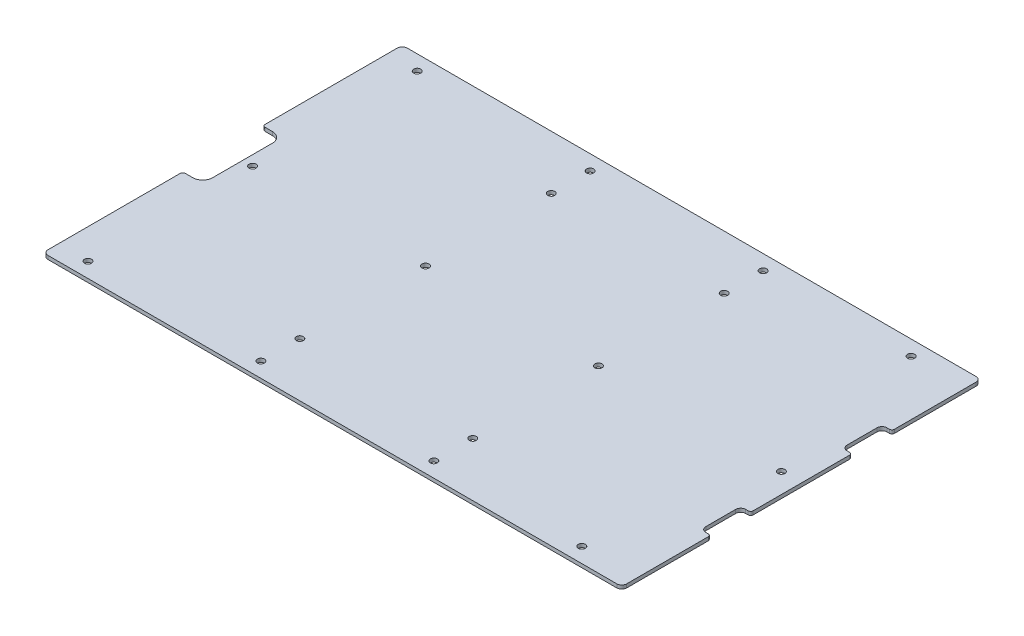
SolidWorks part; units mm, degrees
material "1060 Alloy"
ref_plane "Front" through (0, 0, 0) normal (0, 0, 1) x (1, 0, 0)
ref_plane "Top" through (0, 0, 0) normal (0, 1, 0) x (1, 0, 0)
ref_plane "Right" through (0, 0, 0) normal (1, 0, 0) x (0, 0, -1)
sketch "Sketch1" plane through (0, 0, 0) normal (0, 1, 0) x (1, 0, 0)
  line L0 (-55.0333, 0) -> (-165.1, 0) construction
  line L1 (-180.975, 114.3) -> (180.975, 114.3)
  line L2 (-184.15, 111.125) -> (-184.15, -111.125)
  line L3 (-180.975, -114.3) -> (180.975, -114.3)
  line L4 (184.15, 111.125) -> (184.15, -111.125)
  line L5 (-184.15, 114.3) -> (184.15, -114.3) construction
  line L6 (-184.15, -114.3) -> (184.15, 114.3) construction
  line L7 (-165.1, -104.775) -> (165.1, -104.775) construction
  line L8 (-165.1, -104.775) -> (-165.1, 104.775) construction
  line L9 (-165.1, 104.775) -> (165.1, 104.775) construction
  line L10 (165.1, -104.775) -> (165.1, 104.775) construction
  line L11 (-165.1, -104.775) -> (165.1, 104.775) construction
  line L12 (-165.1, 104.775) -> (165.1, -104.775) construction
  line L13 (-55.0333, -104.775) -> (55.0333, -104.775) construction
  line L14 (-55.0333, -104.775) -> (-55.0333, 104.775) construction
  line L15 (-55.0333, 104.775) -> (55.0333, 104.775) construction
  line L16 (55.0333, -104.775) -> (55.0333, 104.775) construction
  line L17 (-55.0333, -104.775) -> (55.0333, 104.775) construction
  line L18 (-55.0333, 104.775) -> (55.0333, -104.775) construction
  line L19 (55.0333, 0) -> (165.1, 0) construction
  line L20 (-55.0333, 0) -> (55.0333, 0) construction
  line L31 (-55.0291, 80.01) -> (55.0291, 80.01) construction
  line L32 (149.225, -104.775) -> (149.225, 104.775) construction
  line L33 (-55.0291, 80.01) -> (-55.0291, -80.01) construction
  line L34 (-55.0291, -80.01) -> (55.0291, -80.01) construction
  line L35 (55.0291, 80.01) -> (55.0291, -80.01) construction
  line L36 (-55.0291, 80.01) -> (55.0291, -80.01) construction
  line L37 (-55.0291, -80.01) -> (55.0291, 80.01) construction
  circle A0 centre (-165.1, 104.775) radius 2.2479
  circle A1 centre (-55.0333, 104.775) radius 2.2479
  circle A2 centre (55.0333, 104.775) radius 2.2479
  circle A3 centre (165.1, 104.775) radius 2.2479 construction
  circle A4 centre (165.1, -104.775) radius 2.2479 construction
  circle A5 centre (55.0333, -104.775) radius 2.2479
  circle A6 centre (-55.0333, -104.775) radius 2.2479
  circle A7 centre (-165.1, -104.775) radius 2.2479
  circle A12 centre (-55.0333, 0) radius 2.2479
  circle A13 centre (55.0333, 0) radius 2.2479
  arc A14 (184.15, 111.125) -> (180.975, 114.3) centre (180.975, 111.125) ccw
  arc A15 (184.15, -111.125) -> (180.975, -114.3) centre (180.975, -111.125) cw
  arc A16 (-180.975, -114.3) -> (-184.15, -111.125) centre (-180.975, -111.125) cw
  arc A17 (-180.975, 114.3) -> (-184.15, 111.125) centre (-180.975, 111.125) ccw
  circle A24 centre (149.225, -104.775) radius 2.2479
  circle A25 centre (149.225, 104.775) radius 2.2479
  circle A26 centre (55.0291, -80.01) radius 2.2479
  circle A27 centre (-55.0291, -80.01) radius 2.2479
  circle A28 centre (-55.0291, 80.01) radius 2.2479
  circle A29 centre (55.0291, 80.01) radius 2.2479
  circle A30 centre (171.45, 0) radius 2.2479
  circle A31 centre (-165.1, 0) radius 2.2479
  point P0 (0, 0)
  point P6 (0, 0)
  point P11 (0, 0)
  point P28 (0, 0)
  point P29 (0, 0)
  point P32 (0, 0)
  dimension "D5" = 4.4958
  dimension "D8" = 4.4958
  dimension "D11" = 3.175
  dimension "D10" = 12.7
  dimension "D12" = 19.05
  dimension "D13" = 110.0667
  dimension "D1" = 368.3
  dimension "D2" = 228.6
  dimension "D3" = 9.525
  dimension "D4" = 19.05
  dimension "D6" = 160.02
  dimension "D7" = 34.925
  dimension "D9" = 110.0582
extrude "Boss-Extrude1" add sketch "Sketch1" along normal blind 2.286
sketch "Sketch2" plane through (0, 0, 0) normal (0, -1, 0) x (1, 0, 0)
  line L5 (184.15, 111.125) -> (184.15, -111.125) construction
  line L6 (184.15, 57.658) -> (180.975, 57.658)
  line L7 (184.15, 57.658) -> (184.15, 32.258)
  line L8 (184.15, 32.258) -> (180.975, 32.258)
  line L9 (177.8, 54.483) -> (177.8, 35.433)
  line L10 (-184.15, 0) -> (185.7248, 0) construction
  line L11 (-184.15, -111.125) -> (-184.15, 111.125) construction
  line L12 (185.7248, -116.6368) -> (185.7248, 116.6368) construction
  line L13 (177.8, 44.958) -> (184.15, 44.958) construction
  line L14 (184.15, -32.258) -> (180.975, -32.258)
  line L15 (184.15, -57.658) -> (184.15, -32.258)
  line L16 (177.8, -54.483) -> (177.8, -35.433)
  line L17 (184.15, -57.658) -> (180.975, -57.658)
  line L19 (-184.15, 25.4) -> (-177.8, 25.4)
  line L20 (-184.15, 25.4) -> (-184.15, -25.4)
  line L21 (-184.15, -25.4) -> (-177.8, -25.4)
  line L22 (-171.45, 19.05) -> (-171.45, -19.05)
  arc A0 (180.975, -57.658) -> (177.8, -54.483) centre (180.975, -54.483) cw
  arc A1 (177.8, -35.433) -> (180.975, -32.258) centre (180.975, -35.433) cw
  arc A2 (177.8, 35.433) -> (180.975, 32.258) centre (180.975, 35.433) ccw
  arc A3 (177.8, 54.483) -> (180.975, 57.658) centre (180.975, 54.483) cw
  arc A4 (-171.45, -19.05) -> (-177.8, -25.4) centre (-177.8, -19.05) cw
  arc A5 (-171.45, 19.05) -> (-177.8, 25.4) centre (-177.8, 19.05) ccw
  point P20 (177.8, -57.658)
  point P23 (177.8, -32.258)
  point P26 (177.8, 32.258)
  point P29 (177.8, 57.658)
  point P38 (-171.45, 25.4)
  dimension "D4" = 3.175
  dimension "D7" = 6.35
  dimension "D1" = 25.4
  dimension "D2" = 44.958
  dimension "D3" = 6.35
  dimension "D5" = 50.8
  dimension "D6" = 12.7
extrude "Cut-Extrude1" cut sketch "Sketch2" against normal through all
fillet "Fillet1" radius 1.5875 6 edges at (184.15, 1.143, -57.658) (184.15, 1.143, -32.258) (184.15, 1.143, 32.258) (184.15, 1.143, 57.658) (-184.15, 1.143, -25.4) (-184.15, 1.143, 25.4)
